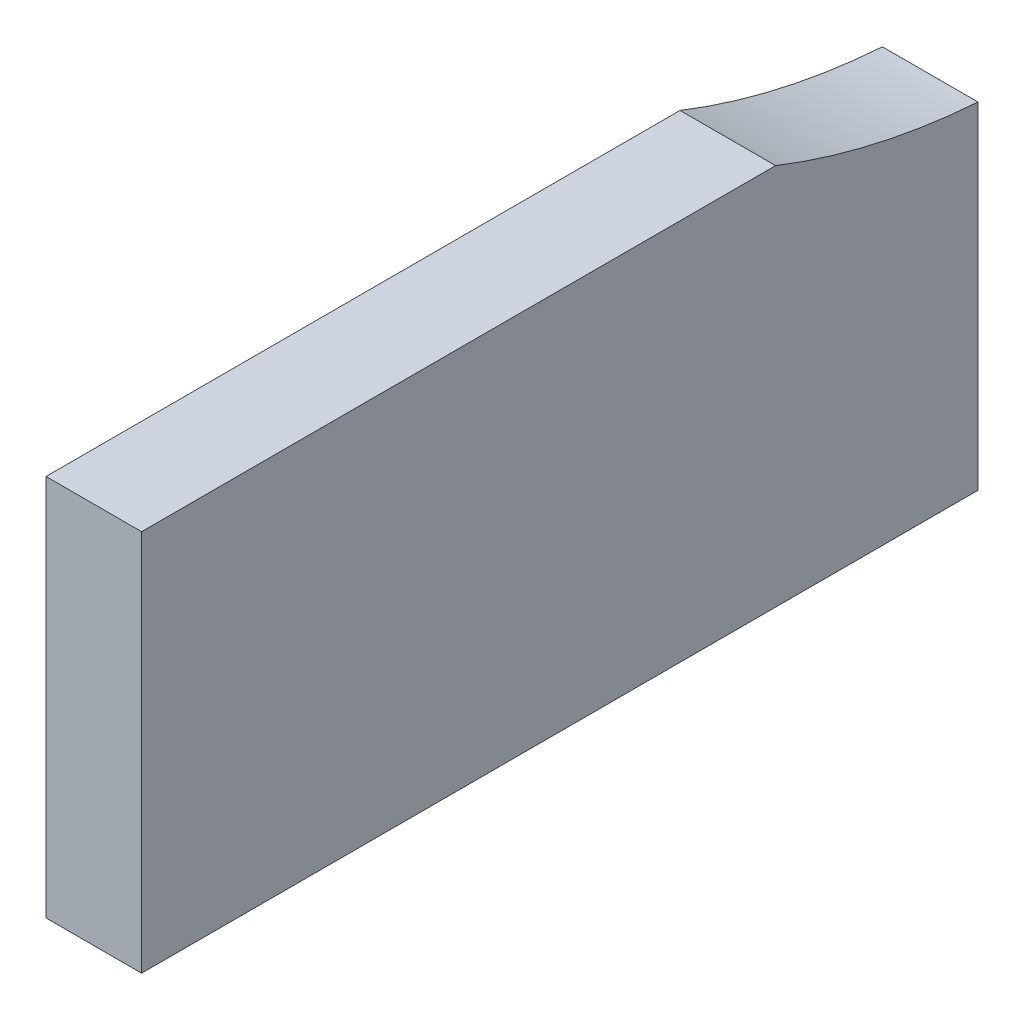
SolidWorks part; units mm, degrees
ref_plane "Front Plane" through (0, 0, 0) normal (0, 0, 1) x (1, 0, 0)
ref_plane "Top Plane" through (0, 0, 0) normal (0, 1, 0) x (1, 0, 0)
ref_plane "Right Plane" through (0, 0, 0) normal (1, 0, 0) x (0, 0, -1)
sketch "Sketch1" plane through (0, 0, 0) normal (0, 0, 1) x (1, 0, 0)
  line L1 (-5, 20) -> (0, 20)
  line L2 (-5, 20) -> (-5, 0)
  line L3 (-5, 0) -> (0, 0)
  line L4 (0, 20) -> (0, 0)
  dimension "D1" = 20
  dimension "D2" = 5
extrude "Boss-Extrude1" add sketch "Sketch1" along normal blind 88.5
sketch "Sketch2" plane through (-5, 0, 0) normal (-1, 0, 0) x (0, 0, 1)
  line L1 (88.5, 0) -> (0, 0)
  line L2 (88.5, 0) -> (88.5, 20)
  line L3 (88.5, 20) -> (0, 20)
  line L4 (0, 0) -> (0, 20)
  line L5 (77.75, 0) -> (6.75, 0)
  line L6 (77.75, 0) -> (77.75, 20)
  line L7 (77.75, 20) -> (6.75, 20)
  line L8 (6.75, 0) -> (6.75, 20)
  line L9 (44.75, 0) -> (39.75, 0)
  line L10 (44.75, 0) -> (44.75, 20)
  line L11 (44.75, 20) -> (39.75, 20)
  line L12 (39.75, 0) -> (39.75, 20)
  dimension "D1" = 71
  dimension "D2" = 6.75
  dimension "D3" = 5
  dimension "D4" = 33
sketch "Sketch5" plane through (0, 0, 0) normal (1, 0, 0) x (0, 0, -1)
  line L0 (-88.5, 0) -> (0, 0) construction
  line L1 (-88.5, 0) -> (-88.5, 20) construction
  circle A0 centre (-42.25, 53) radius 35.5
  dimension "D1" = 71
  dimension "D2" = 53
  dimension "D3" = 46.25
extrude "Cut-Extrude2" cut sketch "Sketch5" against normal blind 35 and the other way blind 35
extrude "Cut-Extrude3" cut sketch "Sketch2" against normal blind 13 contours L12 L5 L10 L7 region at (-5, 10, 42.25)
sketch "Sketch8" plane through (-5, 0, 0) normal (-1, 0, 0) x (0, 0, 1)
  line L1 (39.75, 0) -> (0, 0)
  line L2 (39.75, 0) -> (39.75, 20)
  line L3 (39.75, 20) -> (0, 20)
  line L4 (0, 0) -> (0, 20)
extrude "Cut-Extrude4" cut sketch "Sketch8" against normal blind 13
